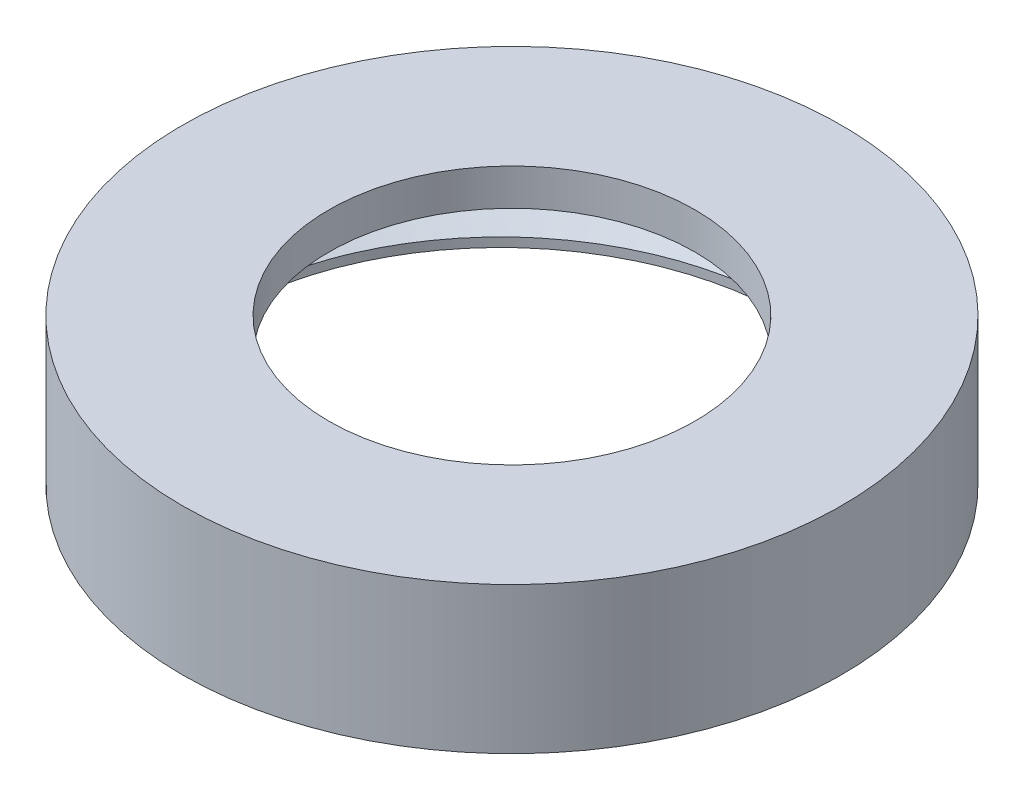
SolidWorks part; units mm, degrees
ref_plane "Front Plane" through (0, 0, 0) normal (0, 0, 1) x (1, 0, 0)
ref_plane "Top Plane" through (0, 0, 0) normal (0, 1, 0) x (1, 0, 0)
ref_plane "Right Plane" through (0, 0, 0) normal (1, 0, 0) x (0, 0, -1)
sketch "Sketch1" plane through (0, 0, 0) normal (0, 1, 0) x (1, 0, 0)
  circle A0 centre (0, 0) radius 7.75
  circle A1 centre (0, 0) radius 9
extrude "Boss-Extrude1" add sketch "Sketch1" along normal blind 3
sketch "Sketch2" plane through (0, 3, 0) normal (0, 1, 0) x (1, 0, 0)
  circle A0 centre (0, 0) radius 9
  circle A1 centre (0, 0) radius 5
extrude "Boss-Extrude2" add sketch "Sketch2" along normal blind 1
thread "Thread2" pitch 1 method cut trim with start face yes trim with end face yes profile "Thread Profile2" start angle 0, offset 1, length 0, pitch 1, diameter 15.5
ref_plane "Plane2" through (7.75, -1, 0) normal (0, 0, 1) x (1, 0, 0)
sketch "Thread Profile2" plane through (7.75, -1, 0) normal (0, 0, 1) x (1, 0, 0)
  line L0 (0, 0) -> (0, 1) construction
  line L1 (0, 0) -> (0.5413, 0.3125)
  line L2 (0.5413, 0.3125) -> (0.5413, 0.4375)
  line L3 (0.5413, 0.4375) -> (0, 0.75)
  line L4 (0.5413, 0.375) -> (0, 0.375) construction
  line L11 (0, 0) -> (0, 0.75)
  point P2 (0, 0)
  dimension "Pitch" = 1
  dimension "Profile_Angle" = 60
  dimension "Profile_Land" = 0.125
  dimension "Profile_Height" = 0.5413
